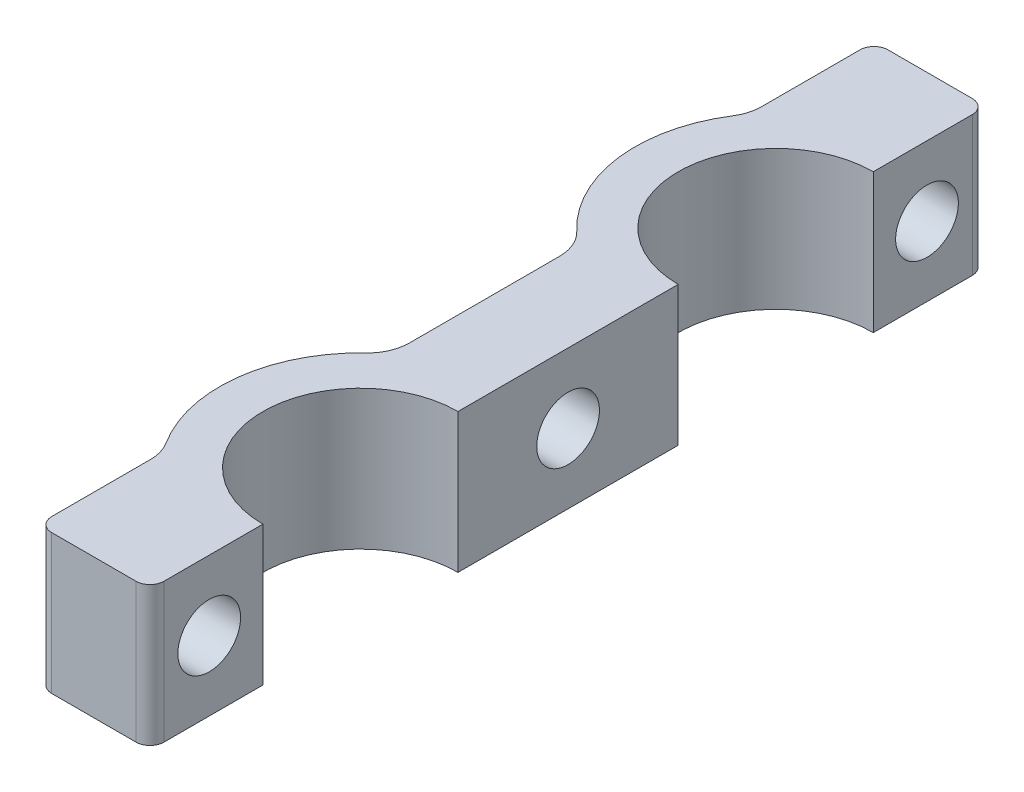
SolidWorks part; units mm, degrees
material "3.1355 (EN-AW 2024)"
ref_plane "Front" through (0, 0, 0) normal (0, 0, 1) x (1, 0, 0)
ref_plane "Top" through (0, 0, 0) normal (0, 1, 0) x (1, 0, 0)
ref_plane "Right" through (0, 0, 0) normal (1, 0, 0) x (0, 0, -1)
sketch "Эскиз1" plane through (0, 0, 0) normal (0, 1, 0) x (1, 0, 0)
  line L0 (0, 0) -> (0, 60) construction
  line L1 (0, 30) -> (-15.0292, 30) construction
  line L2 (0, 0) -> (0, 8)
  line L3 (0, 60) -> (0, 52)
  line L4 (0, 37.8) -> (0, 22.2)
  line L5 (-3, 0) -> (-3, 5.4558)
  line L6 (-3, 35.2558) -> (-3, 24.7442)
  line L7 (-3, 60) -> (-3, 54.5442)
  line L8 (-3, 60) -> (0, 60)
  line L9 (-3, 0) -> (0, 0)
  circle A0 centre (0, 15.1) radius 7.1 construction
  circle A1 centre (0, 44.9) radius 7.1 construction
  arc A2 (0, 8) -> (0, 22.2) centre (0, 15.1) cw
  arc A3 (0, 52) -> (0, 37.8) centre (0, 44.9) ccw
  arc A4 (-3, 5.4558) -> (-3, 24.7442) centre (0, 15.1) cw
  arc A5 (-3, 54.5442) -> (-3, 35.2558) centre (0, 44.9) ccw
  point P9 (0, 22.2)
  dimension "D2" = 15.1
  dimension "D3" = 14.2
  dimension "D1" = 60
  dimension "D4" = 3
extrude "Бобышка-Вытянуть1" add sketch "Эскиз1" along normal blind 10
sketch "Эскиз2" plane through (0, 10, 0) normal (0, 1, 0) x (1, 0, 0)
  line L0 (-3, 60) -> (-8.0498, 60)
  line L1 (-8.0498, 60) -> (-8.0498, 51)
  line L2 (-3, 60) -> (-3, 54.5442)
  line L3 (0, 30) -> (-3, 30) construction
  line L4 (0, 22.2) -> (0, 37.8) construction
  line L5 (-3, 35.2558) -> (-3, 24.7442) construction
  line L6 (-3, 0) -> (-3, 5.4558)
  line L7 (-8.0498, 0) -> (-8.0498, 9)
  line L8 (-3, 0) -> (-8.0498, 0)
  arc A0 (-3, 54.5442) -> (-3, 35.2558) centre (0, 44.9) ccw construction
  arc A1 (-3, 54.5442) -> (-8.0498, 51) centre (0, 44.9) ccw
  arc A2 (-3, 5.4558) -> (-8.0498, 9) centre (0, 15.1) cw
  dimension "D1" = 9
sketch "Эскиз3" plane through (-3, 0, 0) normal (-1, 0, 0) x (0, 0, 1)
  line L0 (-60, 5) -> (-54.7288, 5) construction
  line L1 (-60, 10) -> (-60, 0) construction
  line L3 (-30, 10) -> (-30, 0) construction
  line L4 (-35.2558, 10) -> (-24.7442, 10) construction
  line L5 (-35.2558, 0) -> (-24.7442, 0) construction
  circle A0 centre (-55.75, 5) radius 2.25
  circle A1 centre (-4.25, 5) radius 2.25
  point P6 (-58, 5)
  point P7 (-53.5, 5)
  dimension "D1" = 4.5
  dimension "D2" = 2
extrude "Бобышка-Вытянуть2" add sketch "Эскиз2" against normal up to surface (10 mm away) up to face at (-3.8667, 0, -30)
extrude "Вырез-Вытянуть1" cut sketch "Эскиз3" against normal through all and the other way up to surface (5.0498 mm away) other way up to face at (-8.0498, 5, -55.5)
sketch "Эскиз7" plane through (-3, 0, 0) normal (0, 1, 0) x (0, 0, 1)
  line L0 (-36.7753, -3) -> (-23.2247, -3)
  line L1 (-35.2558, 0) -> (-24.7442, 0) construction
  line L2 (-35.2558, 0) -> (-24.7442, 0)
  arc A0 (-51, -5.0498) -> (-35.2558, 0) centre (-44.9, 3) ccw construction
  arc A1 (-24.7442, 0) -> (-9, -5.0498) centre (-15.1, 3) ccw construction
  arc A2 (-36.7753, -3) -> (-35.2558, 0) centre (-44.9, 3) ccw
  arc A3 (-24.7442, 0) -> (-23.2247, -3) centre (-15.1, 3) ccw
  dimension "D1" = 3
extrude "Бобышка-Вытянуть4" add sketch "Эскиз7" along normal through all
sketch "Эскиз4" plane through (-6, 0, 0) normal (-1, 0, 0) x (0, 0, 1)
  line L0 (-30, 10) -> (-30, 0) construction
  line L3 (-36.7753, 10) -> (-23.2247, 10) construction
  line L4 (-36.7753, 0) -> (-23.2247, 0) construction
  circle A0 centre (-30, 5) radius 2.25
  dimension "D1" = 4.5
extrude "Вырез-Вытянуть2" cut sketch "Эскиз4" against normal through all
fillet "Скругление1" radius 3 4 edges at (-8.0498, 5, -9) (-8.0498, 5, -51) (-6, 5, -23.2247) (-6, 5, -36.7753)
fillet "Скругление2" radius 1 2 edges at (-8.0498, 5, -60) (-8.0498, 5, 0)
sketch "Эскиз5" plane through (0, 0, 0) normal (0, -1, 0) x (1, 0, 0)
  line L0 (0, -8) -> (0, -8.1)
  line L1 (0, -51.9) -> (0, -52)
  line L2 (0, -37.8) -> (0, -37.9)
  line L3 (0, -22.1) -> (0, -22.2)
  arc A0 (0, -8) -> (0, -22.2) centre (0, -15.1) ccw construction
  arc A1 (0, -37.8) -> (0, -52) centre (0, -44.9) ccw construction
  arc A2 (0, -8) -> (0, -22.2) centre (0, -15.1) ccw
  arc A3 (0, -37.8) -> (0, -52) centre (0, -44.9) ccw
  arc A4 (0, -8.1) -> (0, -22.1) centre (0, -15.1) ccw
  arc A5 (0, -37.9) -> (0, -51.9) centre (0, -44.9) ccw
  dimension "D1" = 0.1
extrude "Бобышка-Вытянуть3" add sketch "Эскиз5" against normal through all
sketch "Эскиз6" plane through (0, 0, 0) normal (0, -1, 0) x (1, 0, 0)
  line L0 (-10.1, -44.9) -> (-10.1, -60) construction
  line L1 (-7.0498, -60) -> (-10.1, -60) construction
  arc A0 (-6.9389, -37.561) -> (-8.5193, -50.325) centre (0, -44.9) ccw construction
fillet "Скругление3" radius 1 2 edges at (0, 5, -60) (0, 5, 0)
equation "\"D2@Эскиз1\"=8+\"D3@Эскиз1\"/2"
